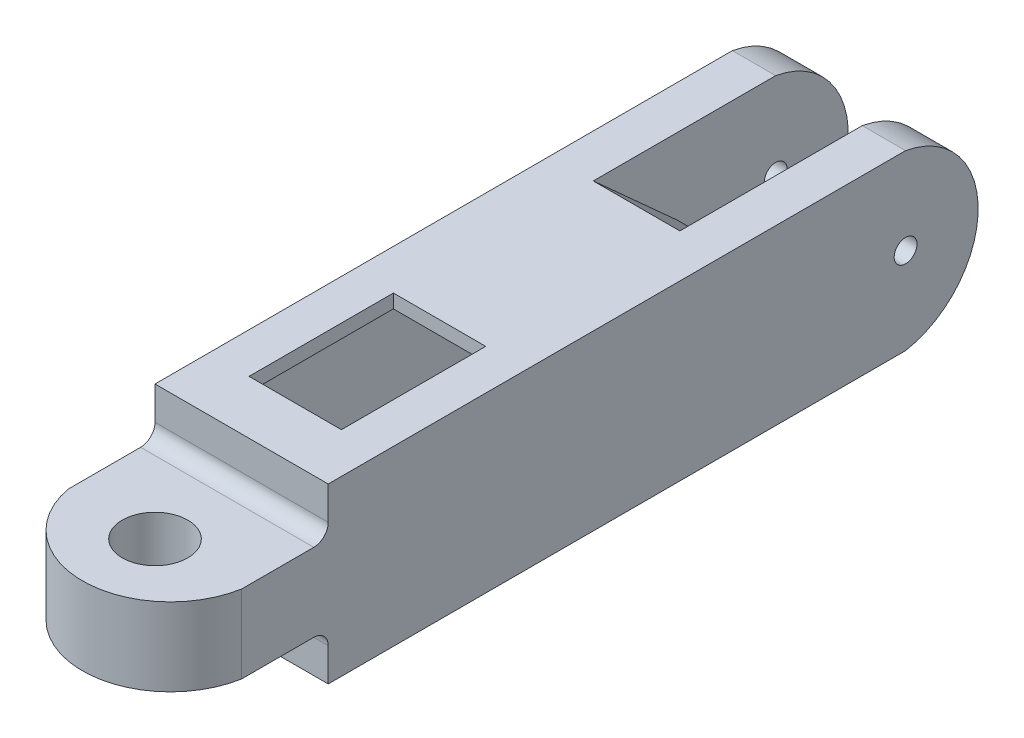
SolidWorks part; units mm, degrees
ref_plane "Front Plane" through (0, 0, 0) normal (0, 0, 1) x (1, 0, 0)
ref_plane "Top Plane" through (0, 0, 0) normal (0, 1, 0) x (1, 0, 0)
ref_plane "Right Plane" through (0, 0, 0) normal (1, 0, 0) x (0, 0, -1)
sketch "Sketch2" plane through (0, 0, 0) normal (0, 0, 1) x (1, 0, 0)
  line L1 (-30, 30) -> (30, 30)
  line L2 (-30, 30) -> (-30, -30)
  line L3 (-30, -30) -> (30, -30)
  line L4 (30, 30) -> (30, -30)
  line L5 (-30, 30) -> (30, -30) construction
  line L6 (-30, -30) -> (30, 30) construction
  point P0 (0, 0)
  dimension "D1" = 60
  dimension "D2" = 60
extrude "Boss-Extrude1" add sketch "Sketch2" along normal blind 170
ref_plane "Plane1" through (0, 0, 0) normal (0, 0, -1) x (-1, 0, 0)
sketch "Sketch3" plane through (0, 0, 0) normal (0, 0, -1) x (-1, 0, 0)
  line L0 (-30, 30) -> (30, 30) construction
  line L1 (30, -30) -> (15, -30)
  line L2 (30, -30) -> (30, 30)
  line L3 (30, 30) -> (15, 30)
  line L4 (15, -30) -> (15, 30)
  line L5 (30, -30) -> (-30, -30) construction
  line L6 (-30, 30) -> (-15, 30)
  line L7 (-30, 30) -> (-30, -30)
  line L8 (-30, -30) -> (-15, -30)
  line L9 (-15, 30) -> (-15, -30)
  dimension "D1" = 15
  dimension "D2" = 15
extrude "Boss-Extrude2" add sketch "Sketch3" along normal blind 30
ref_plane "Plane2" through (30, 0, 0) normal (1, 0, 0) x (0, 0, -1)
sketch "Sketch4" plane through (30, 0, 0) normal (1, 0, 0) x (0, 0, -1)
  line L0 (30, 30) -> (30, -30)
  arc A0 (30, 30) -> (30, -30) centre (24.6689, 0) cw
  dimension "D1" = 30.47
extrude "Boss-Extrude3" add sketch "Sketch4" against normal blind 15
ref_plane "Plane3" through (-30, 0, 0) normal (-1, 0, 0) x (0, 0, 1)
sketch "Sketch5" plane through (-30, 0, 0) normal (-1, 0, 0) x (0, 0, 1)
  line L0 (-30, -30) -> (-30, 30)
  arc A0 (-30, -30) -> (-30, 30) centre (-24.6689, 0) cw
  dimension "D1" = 30.47
extrude "Boss-Extrude4" add sketch "Sketch5" against normal blind 15
ref_plane "Plane4" through (0, 0, 170) normal (0, 0, 1) x (1, 0, 0)
sketch "Sketch6" plane through (0, 0, 170) normal (0, 0, 1) x (1, 0, 0)
  line L0 (30, -30) -> (30, 30) construction
  line L1 (-30, 13.5) -> (30, 13.5)
  line L2 (-30, 13.5) -> (-30, -13.5)
  line L3 (-30, -13.5) -> (30, -13.5)
  line L4 (30, 13.5) -> (30, -13.5)
  line L5 (-30, 13.5) -> (30, -13.5) construction
  line L6 (-30, -13.5) -> (30, 13.5) construction
  point P0 (0, 0)
  dimension "D1" = 27
extrude "Boss-Extrude5" add sketch "Sketch6" along normal blind 30
ref_plane "Plane5" through (0, 13.5, 0) normal (0, 1, 0) x (1, 0, 0)
sketch "Sketch7" plane through (0, 13.5, 0) normal (0, 1, 0) x (1, 0, 0)
  line L0 (30, -200) -> (-30, -200)
  arc A0 (30, -200) -> (-30, -200) centre (0, -194.6689) cw
  dimension "D1" = 30.47
extrude "Boss-Extrude6" add sketch "Sketch7" against normal blind 27
ref_plane "Plane6" through (0, 0, 170) normal (0, 0, 1) x (1, 0, 0)
sketch "Sketch8" plane through (0, 0, 170) normal (0, 0, 1) x (1, 0, 0)
  line L1 (-25.25, -25.25) -> (25.25, -25.25)
  line L2 (-25.25, -25.25) -> (-25.25, 25.25)
  line L3 (-25.25, 25.25) -> (25.25, 25.25)
  line L4 (25.25, -25.25) -> (25.25, 25.25)
  line L5 (-25.25, -25.25) -> (25.25, 25.25) construction
  line L6 (-25.25, 25.25) -> (25.25, -25.25) construction
  point P0 (0, 0)
  dimension "D1" = 50.5
  dimension "D2" = 50.5
extrude "Cut-Extrude2" cut sketch "Sketch8" against normal blind 130 and the other way blind 5 from offset 10 contours L3 L4 L1 L2 offset against normal yes
ref_plane "Plane7" through (0, -13.5, 0) normal (0, -1, 0) x (-1, 0, 0)
sketch "Sketch9" plane through (0, -13.5, 0) normal (0, -1, 0) x (-1, 0, 0)
  line L0 (30, -170) -> (-30, -170) construction
  circle A0 centre (0, -200) radius 11.35
  dimension "D1" = 22.7
  dimension "D2" = 30
extrude "Cut-Extrude3" cut sketch "Sketch9" against normal blind 130
ref_plane "Plane8" through (30, 0, 0) normal (1, 0, 0) x (0, 0, -1)
ref_plane "Plane9" through (15, 0, 0) normal (-1, 0, 0) x (0, 0, 1)
sketch "Sketch11" plane through (15, 0, 0) normal (-1, 0, 0) x (0, 0, 1)
  line L0 (0, -30) -> (0, 30) construction
  circle A0 centre (-30, 0) radius 3.95
  dimension "D2" = 7.9
  dimension "D1" = 30
extrude "Cut-Extrude4" cut sketch "Sketch11" against normal through all
ref_plane "Plane10" through (-15, 0, 0) normal (1, 0, 0) x (0, 0, -1)
sketch "Sketch12" plane through (-15, 0, 0) normal (1, 0, 0) x (0, 0, -1)
  line L0 (0, 30) -> (0, -30) construction
  circle A0 centre (30, 0) radius 3.95
  dimension "D1" = 30
  dimension "D2" = 7.9
extrude "Cut-Extrude5" cut sketch "Sketch12" against normal through all
sketch "Sketch14" plane through (-15, 0, 0) normal (1, 0, 0) x (0, 0, -1)
  line L0 (0, 0) -> (0, 30)
  line L1 (0, 30) -> (0, -30) construction
  line L2 (0, 30) -> (-33.1884, 30)
  line L3 (-33.1884, 30) -> (0, 0)
  line L4 (0, 0) -> (0, -30)
  line L5 (0, -30) -> (-33.1884, -30)
  line L6 (-33.1884, -30) -> (0, 0)
  line M3 (0, 30) -> (0, -30)
extrude "Cut-Extrude7" cut sketch "Sketch14" along normal blind 30 contours L6 L5 M3 | L2 L3 M3 region at (-15, 20, 11.0628) region at (-15, -20, 11.0628)
fillet "Fillet2" radius 5 1 edges at (0, 0, 0)
fillet "Fillet3" radius 5 2 edges at (0, -13.5, 170) (0, 13.5, 170)
ref_plane "Plane11" through (0, 30, 0) normal (0, 1, 0) x (1, 0, 0)
sketch "Sketch16" plane through (0, 30, 0) normal (0, 1, 0) x (1, 0, 0)
  line L0 (30, -170) -> (30, 30) construction
  line L1 (16, -101.43) -> (-16, -101.43)
  line L2 (16, -101.43) -> (16, -151.43)
  line L3 (16, -151.43) -> (-16, -151.43)
  line L4 (-16, -101.43) -> (-16, -151.43)
  line L5 (0, -139.93) -> (-16, -151.43) construction
  line L6 (16, -151.43) -> (0, -139.93) construction
  line L7 (30, -170) -> (-30, -170) construction
  line L8 (0, -139.93) -> (-16, -139.93)
  line L9 (0, -139.93) -> (0, -151.43)
  line L10 (0, -139.93) -> (0, -151.43)
  line L11 (0, -139.93) -> (0, -199.93)
  point P0 (0, -139.93)
  dimension "D1" = 50
  dimension "D2" = 32
  dimension "D3" = 14
  dimension "D4" = 11.5
  dimension "D5" = 16
  dimension "D6" = 18.57
  dimension "D7" = 60
extrude "Cut-Extrude8" cut sketch "Sketch16" against normal blind 71 contours L8 L9 L3 L2 L1 L4 | L9 L8 L4 L3 region at (1.0395, 30, 123.9286) region at (-8, 30, 145.68)
